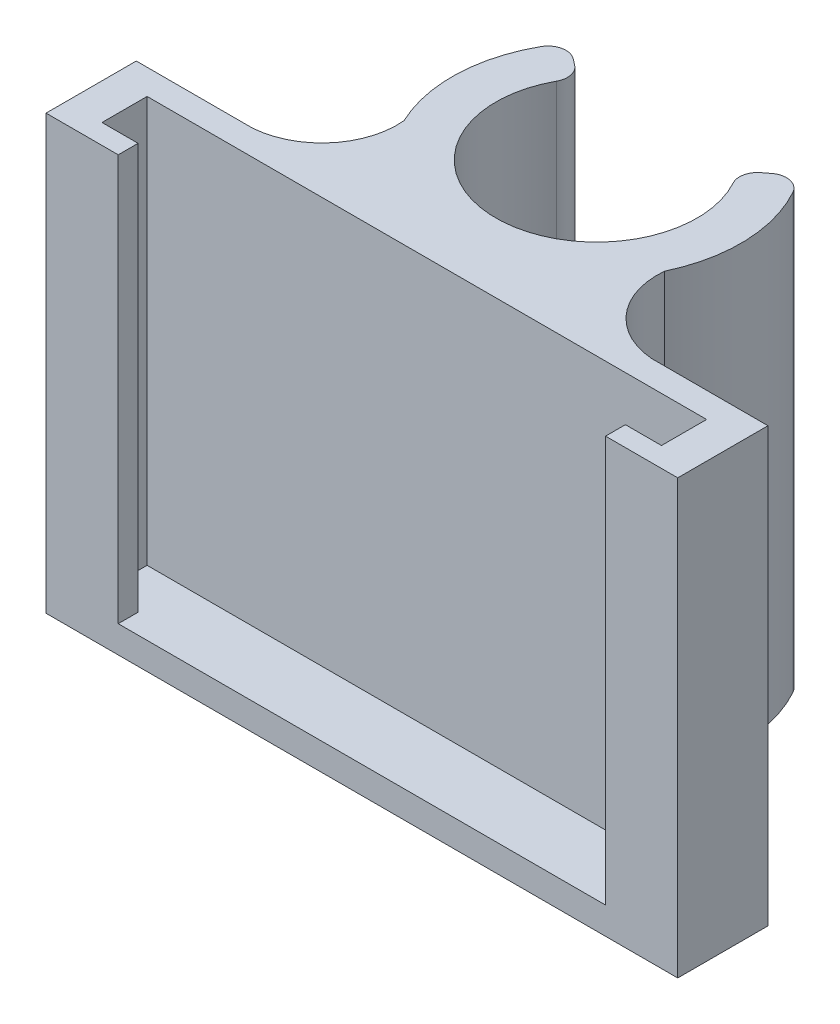
SolidWorks part; units mm, degrees
material "ABS"
ref_plane "Front Plane" through (0, 0, 0) normal (0, 0, 1) x (1, 0, 0)
ref_plane "Top Plane" through (0, 0, 0) normal (0, 1, 0) x (1, 0, 0)
ref_plane "Right Plane" through (0, 0, 0) normal (1, 0, 0) x (0, 0, -1)
sketch "Sketch1" plane through (0, 0, 0) normal (0, 1, 0) x (1, 0, 0)
  line L0 (0, -29.4402) -> (0, 28.6728) construction
  line L9 (22.0972, -16) -> (35, -16)
  line L10 (35, -16) -> (35, -26)
  line L11 (35, -26) -> (27, -26)
  line L12 (27, -26) -> (27, -23.8)
  line L13 (27, -23.8) -> (31, -23.8)
  line L14 (31, -23.8) -> (31, -18.8)
  line L15 (31, -18.8) -> (-31, -18.8)
  line L16 (-31, -23.8) -> (-31, -18.8)
  line L17 (-22.0972, -16) -> (-35, -16)
  line L18 (-27, -26) -> (-27, -23.8)
  line L19 (-35, -26) -> (-27, -26)
  line L20 (-27, -23.8) -> (-31, -23.8)
  line L21 (-35, -16) -> (-35, -26)
  line L22 (-12.7061, 9.724) -> (-8.8545, 6.7764)
  line L23 (12.7061, 9.724) -> (8.8545, 6.7764)
  arc A1 (-8.8545, 6.7764) -> (8.8545, 6.7764) centre (0, 0) ccw
  arc A2 (-12.7061, 9.724) -> (-14.441, -6.8889) centre (0, 0) ccw
  arc A3 (22.0972, -16) -> (14.441, -6.8889) centre (22.7402, -7.6874) cw
  arc A4 (14.441, -6.8889) -> (12.7061, 9.724) centre (0, 0) ccw
  arc A5 (-22.0972, -16) -> (-14.441, -6.8889) centre (-22.7402, -7.6874) ccw
  point P3 (11.7845, 10.8224)
  point P8 (12.7061, 9.724)
  point P30 (0, -18.8)
  dimension "D1" = 5
  dimension "D2" = 22.3
  dimension "D3" = 32
  dimension "D8" = 31
  dimension "D9" = 4
  dimension "D10" = 10
  dimension "D11" = 2.8
  dimension "D12" = 4
extrude "Boss-Extrude1" add sketch "Sketch1" along normal blind 45
fillet "Fillet2" radius 2 4 edges at (8.8545, 22.5, -6.7764) (12.7061, 22.5, -9.724) (-12.7061, 22.5, -9.724) (-8.8545, 22.5, -6.7764)
sketch "Sketch2" plane through (0, 0, 0) normal (0, -1, 0) x (1, 0, 0)
  line L0 (22.0972, 16) -> (35, 16)
  line L1 (-35, 16) -> (-22.0972, 16)
  line L2 (-35, 16) -> (-35, 26)
  line L3 (-35, 26) -> (35, 26)
  line L4 (35, 16) -> (35, 26)
  line L15 (10.3213, -7.8989) -> (11.0038, -8.4212)
  line L16 (22.0972, 16) -> (35, 16)
  line L17 (35, 16) -> (35, 26)
  line L18 (35, 26) -> (27, 26)
  line L19 (27, 26) -> (27, 23.8)
  line L20 (27, 23.8) -> (31, 23.8)
  line L21 (31, 23.8) -> (31, 18.8)
  line L22 (31, 18.8) -> (-31, 18.8)
  line L23 (-31, 18.8) -> (-31, 23.8)
  line L24 (-31, 23.8) -> (-27, 23.8)
  line L25 (-27, 23.8) -> (-27, 26)
  line L26 (-27, 26) -> (-35, 26)
  line L27 (-35, 26) -> (-35, 16)
  line L28 (-35, 16) -> (-22.0972, 16)
  line L29 (-11.0038, -8.4212) -> (-10.3213, -7.8989)
  line L30 (10.3213, -7.8989) -> (11.0038, -8.4212)
  line L31 (22.0972, 16) -> (35, 16)
  line L32 (35, 16) -> (35, 26)
  line L42 (-35, 26) -> (-35, 16)
  line L43 (-35, 16) -> (-22.0972, 16)
  line L44 (-11.0038, -8.4212) -> (-10.3213, -7.8989)
  arc A9 (9.7822, -5.3509) -> (-9.7822, -5.3509) centre (0, 0) ccw
  arc A10 (9.7822, -5.3509) -> (10.3213, -7.8989) centre (11.5368, -6.3107) ccw
  arc A11 (11.0038, -8.4212) -> (13.9649, -7.8091) centre (12.2193, -6.833) ccw
  arc A12 (13.9649, -7.8091) -> (14.441, 6.8889) centre (0, 0) ccw
  arc A13 (22.0972, 16) -> (14.441, 6.8889) centre (22.7402, 7.6874) ccw
  arc A14 (-14.441, 6.8889) -> (-22.0972, 16) centre (-22.7402, 7.6874) ccw
  arc A15 (-14.441, 6.8889) -> (-13.9649, -7.8091) centre (0, 0) ccw
  arc A16 (-13.9649, -7.8091) -> (-11.0038, -8.4212) centre (-12.2193, -6.833) ccw
  arc A17 (-10.3213, -7.8989) -> (-9.7822, -5.3509) centre (-11.5368, -6.3107) ccw
  arc A18 (9.7822, -5.3509) -> (-9.7822, -5.3509) centre (0, 0) ccw
  arc A19 (9.7822, -5.3509) -> (10.3213, -7.8989) centre (11.5368, -6.3107) ccw
  arc A20 (11.0038, -8.4212) -> (13.9649, -7.8091) centre (12.2193, -6.833) ccw
  arc A21 (13.9649, -7.8091) -> (14.441, 6.8889) centre (0, 0) ccw
  arc A22 (22.0972, 16) -> (14.441, 6.8889) centre (22.7402, 7.6874) ccw
  arc A23 (-14.441, 6.8889) -> (-22.0972, 16) centre (-22.7402, 7.6874) ccw
  arc A24 (-14.441, 6.8889) -> (-13.9649, -7.8091) centre (0, 0) ccw
  arc A25 (-13.9649, -7.8091) -> (-11.0038, -8.4212) centre (-12.2193, -6.833) ccw
  arc A26 (-10.3213, -7.8989) -> (-9.7822, -5.3509) centre (-11.5368, -6.3107) ccw
  arc M29 (-9.7822, -5.3509) -> (9.7822, -5.3509) centre (0, 0) cw
  arc M30 (9.7822, -5.3509) -> (10.3213, -7.8989) centre (11.5368, -6.3107) ccw
  line M31 (10.3213, -7.8989) -> (11.0038, -8.4212)
  arc M32 (11.0038, -8.4212) -> (13.9649, -7.8091) centre (12.2193, -6.833) ccw
  arc M33 (13.9649, -7.8091) -> (14.441, 6.8889) centre (0, 0) ccw
  arc M34 (14.441, 6.8889) -> (22.0972, 16) centre (22.7402, 7.6874) cw
  line M35 (22.0972, 16) -> (35, 16)
  line M36 (35, 16) -> (35, 26)
  line M37 (35, 26) -> (27, 26)
  line M38 (27, 26) -> (27, 23.8)
  line M39 (27, 23.8) -> (31, 23.8)
  line M40 (31, 23.8) -> (31, 18.8)
  line M41 (31, 18.8) -> (-31, 18.8)
  line M42 (-31, 18.8) -> (-31, 23.8)
  line M43 (-31, 23.8) -> (-27, 23.8)
  line M44 (-27, 23.8) -> (-27, 26)
  line M45 (-27, 26) -> (-35, 26)
  line M46 (-35, 26) -> (-35, 16)
  line M47 (-35, 16) -> (-22.0972, 16)
  arc M48 (-22.0972, 16) -> (-14.441, 6.8889) centre (-22.7402, 7.6874) cw
  arc M49 (-14.441, 6.8889) -> (-13.9649, -7.8091) centre (0, 0) ccw
  arc M50 (-13.9649, -7.8091) -> (-11.0038, -8.4212) centre (-12.2193, -6.833) ccw
  line M51 (-11.0038, -8.4212) -> (-10.3213, -7.8989)
  arc M52 (-10.3213, -7.8989) -> (-9.7822, -5.3509) centre (-11.5368, -6.3107) ccw
  dimension "D1" = 0
extrude "Boss-Extrude2" add sketch "Sketch2" along normal blind 3 contours M52 M29 M30 M31 M32 M33 M34 M35 M36 M37 M38 M39 M40 M41 M42 M43 M44 M45 M46 M47 M48 M49 M50 M51 | L3 M44 M43 M42 M41 M40 M39 M38 region at (0, 0, 12.0728) region at (0, 0, 22.2974)
